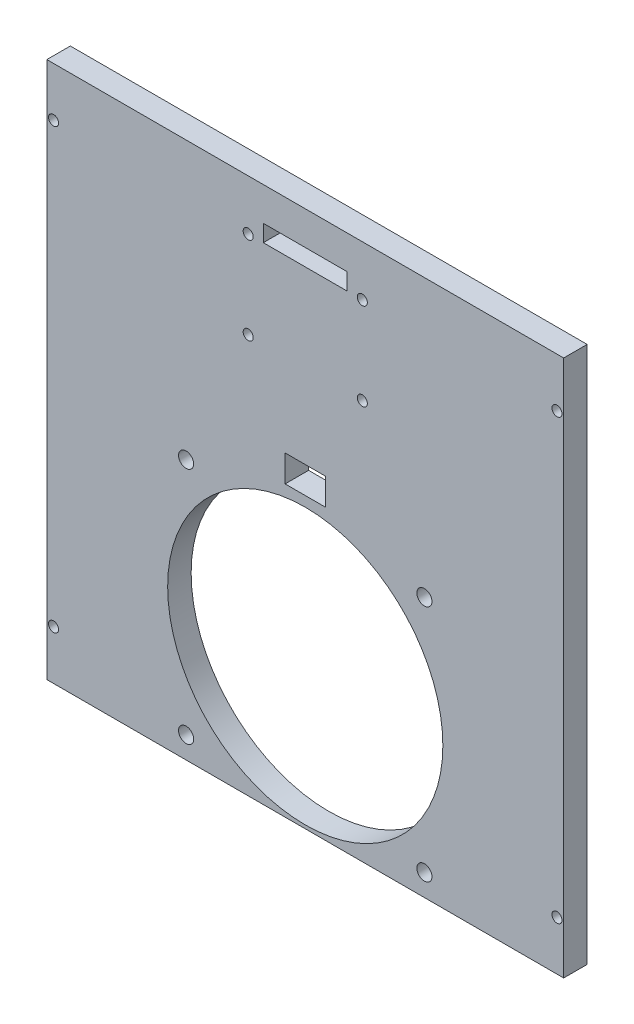
SolidWorks part; units mm, degrees
ref_plane "Piano frontale" through (0, 0, 0) normal (0, 0, 1) x (1, 0, 0)
ref_plane "Piano superiore" through (0, 0, 0) normal (0, 1, 0) x (1, 0, 0)
ref_plane "Piano destro" through (0, 0, 0) normal (1, 0, 0) x (0, 0, -1)
sketch "Schizzo1" plane through (0, 0, 0) normal (0, 0, 1) x (1, 0, 0)
  line L0 (-75, 80) -> (-75, -80) construction
  line L1 (77, -80) -> (-77, -80)
  line L2 (77, -80) -> (77, 80)
  line L3 (77, 80) -> (-77, 80)
  line L4 (-77, -80) -> (-77, 80)
  line L5 (77, -80) -> (-77, 80) construction
  line L6 (77, 80) -> (-77, -80) construction
  line L7 (0, 0) -> (-77, 0) construction
  line L8 (0, 0) -> (0, 80) construction
  circle A1 centre (-75, 65.3439) radius 1.5
  circle A2 centre (75, 65.3439) radius 1.5
  circle A3 centre (75, -65.3439) radius 1.5
  circle A4 centre (-75, -65.3439) radius 1.5
  point P0 (0, 0)
  dimension "D4" = 3
  dimension "D1" = 154
  dimension "D2" = 160
  dimension "D3" = 4
  dimension "D5" = 14.6561
extrude "Estrusione-Estrusione1" add sketch "Schizzo1" along normal blind 7
sketch "Schizzo2" plane through (0, 0, 0) normal (0, 0, -1) x (-1, 0, 0)
  line L0 (32, -38) -> (0, -38) construction
  line L1 (0, -38) -> (0, 3) construction
  line L2 (0, -38) -> (35.5, -2.5) construction
  line L10 (0, -80) -> (0, 80) construction
  line L11 (77, -80) -> (-77, -80) construction
  line L12 (-77, 80) -> (77, 80) construction
  line L13 (0, -38) -> (0, 10) construction
  line L15 (-6, 6) -> (6, 6)
  line L20 (-6, 6) -> (-6, 14)
  line L21 (-6, 14) -> (6, 14)
  line L22 (6, 6) -> (6, 14)
  line L23 (-6, 6) -> (6, 14) construction
  line L24 (-6, 14) -> (6, 6) construction
  circle A0 centre (0, -38) radius 41
  circle A1 centre (35.5, -2.5) radius 2.25
  circle A2 centre (35.5, -73.5) radius 2.25
  circle A3 centre (-35.5, -2.5) radius 2.25
  circle A4 centre (-35.5, -73.5) radius 2.25
  dimension "D2" = 4.5
  dimension "D7" = 82
  dimension "D9" = 8
  dimension "D10" = 12
  dimension "D1" = 45
  dimension "D3" = 0
  dimension "D4" = 42
  dimension "D5" = 32
  dimension "D6" = 50.2046
  dimension "D8" = 48
extrude "Taglio-Estrusione1" cut sketch "Schizzo2" against normal blind 10
sketch "Schizzo3" plane through (0, 0, 0) normal (0, 0, -1) x (-1, 0, 0)
  line L0 (0, 80) -> (0, 14) construction
  line L1 (-77, 80) -> (77, 80) construction
  line L2 (6, 14) -> (-6, 14) construction
  line L3 (0, 65) -> (17, 65) construction
  line L4 (17, 65) -> (17, 39) construction
  line L5 (12.5, 65) -> (-12.5, 65)
  line L9 (12.5, 65) -> (12.5, 70)
  line L10 (12.5, 70) -> (-12.5, 70)
  line L11 (-12.5, 70) -> (-12.5, 65)
  circle A0 centre (17, 65) radius 1.5
  circle A1 centre (17, 39) radius 1.5
  circle A2 centre (-17, 39) radius 1.5
  circle A3 centre (-17, 65) radius 1.5
  point P18 (0, 65)
  dimension "D3" = 3
  dimension "D5" = 3
  dimension "D1" = 15
  dimension "D2" = 17
  dimension "D4" = 26
  dimension "D6" = 25
  dimension "D7" = 5
extrude "Taglio-Estrusione2" cut sketch "Schizzo3" against normal blind 10
sketch "Schizzo4" plane through (0, 0, 0) normal (0, 0, -1) x (-1, 0, 0)
  line L0 (0, 3) -> (0, 80) construction
  line L1 (-77, 80) -> (77, 80) construction
  line L2 (17, 39) -> (-17, 39) construction
  line L3 (0, 37) -> (8, 37) construction
  circle A0 centre (0, -38) radius 41 construction
  circle A1 centre (8, 37) radius 1.5
  circle A2 centre (8, 37) radius 3
  circle A3 centre (-8, 37) radius 3
  circle A4 centre (-8, 37) radius 1.5
  dimension "D2" = 3
  dimension "D4" = 6
  dimension "D1" = 8
  dimension "D3" = 2
extrude "Estrusione-Estrusione2" add sketch "Schizzo4" along normal blind 4.5
fillet "Raccordo1" radius 2 2 edges at (11, 37, 0) (-5, 37, 0)
